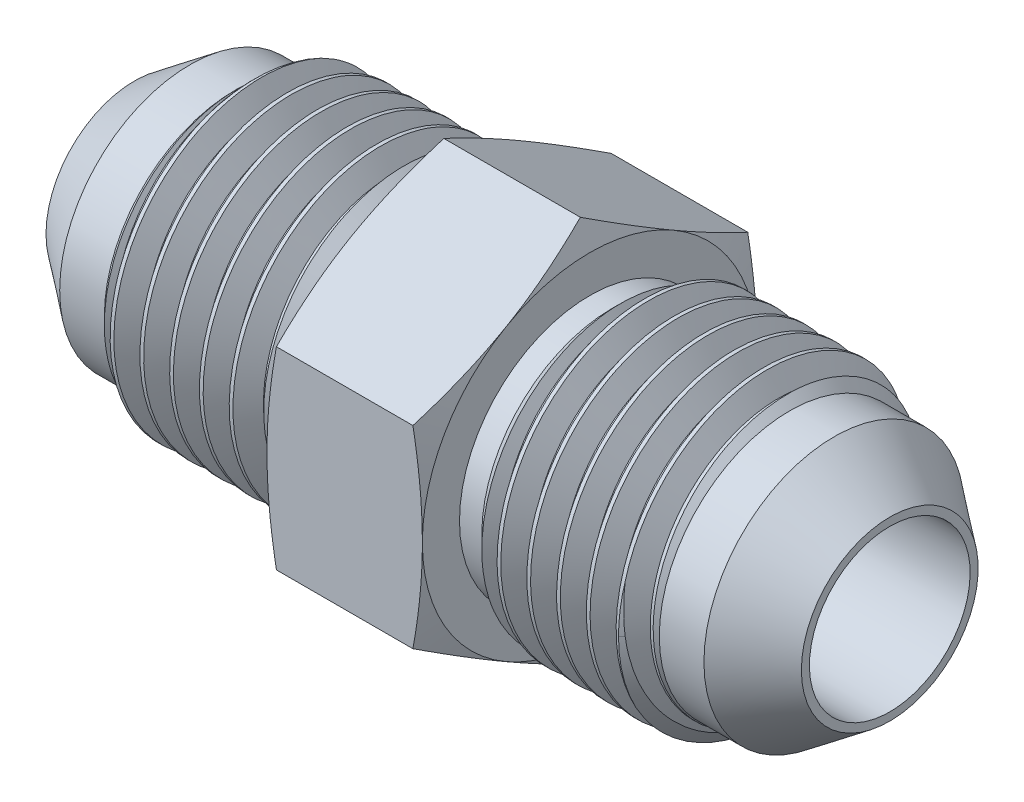
SolidWorks part; units mm, degrees
ref_plane "Front" through (0, 0, 0) normal (0, 0, 1) x (1, 0, 0)
ref_plane "Top" through (0, 0, 0) normal (0, 1, 0) x (1, 0, 0)
ref_plane "Right" through (0, 0, 0) normal (1, 0, 0) x (0, 0, -1)
sketch "Sketch6" plane through (0, 0, 0) normal (0, 0, 1) x (1, 0, 0)
  line L1 (17.907, 7.1437) -> (17.907, -7.1437) construction
  line L2 (-17.907, 0) -> (17.907, 0)
  line L4 (-17.907, 0) -> (-17.907, 7.1438)
  line L5 (-17.907, 7.1438) -> (17.907, 7.1437)
  line L6 (17.907, 0) -> (17.907, 7.1437)
  point P4 (3.683, 0)
  point P6 (-3.683, 0)
  dimension "Straight Dia" = 14.2875
  dimension "Length" = 35.814
  dimension "L1" = 14.224
  dimension "D1" = 14.224
revolve "Revolve3" add sketch "Sketch6" angle 360 about L2
sketch "Sketch14" plane through (-17.907, 0, 0) normal (-1, 0, 0) x (0, 0, 1)
  circle A0 centre (0, 0) radius 7.1438
  circle A2 centre (0, 0) radius 7.1438 construction
curve "Helix/Spiral1" pitch 1.4111 height 37.2251 radius 7.1438 centre (-17.907, 0, 0) axis (1, 0, 0) start towards (0, 1, 0) parameters "Pitch"=1.4111
sketch "Sketch15" plane through (0, 0, 0) normal (0, 0, 1) x (1, 0, 0)
  line L0 (-19.1417, 7.1438) -> (-17.907, 7.1438)
  line L1 (-17.907, 7.1438) -> (-18.4362, 6.2272)
  line L2 (-18.4362, 6.2272) -> (-18.6126, 6.2272)
  line L3 (-18.6126, 6.2272) -> (-19.1417, 7.1438)
  line L4 (-18.5244, 6.2272) -> (-18.5244, 7.1438) construction
  line L5 (-18.8771, 6.6855) -> (-18.1716, 6.6855) construction
  dimension "D1" = 60
  dimension "D2" = 0.1764
  dimension "D3" = 0.7056
sweep "Cut-Sweep1" cut profiles "Sketch15" path "Helix/Spiral1" align with end faces yes
ref_plane "Plane1" through (-3.683, 0, 0) normal (1, 0, 0) x (0, 0, -1)
sketch "Sketch12" plane through (-3.683, 0, 0) normal (1, 0, 0) x (0, 0, -1)
  line L1 (0, 9.1654) -> (-7.9375, 4.5827)
  line L2 (-7.9375, 4.5827) -> (-7.9375, -4.5827)
  line L3 (-7.9375, -4.5827) -> (0, -9.1654)
  line L4 (0, -9.1654) -> (7.9375, -4.5827)
  line L5 (7.9375, -4.5827) -> (7.9375, 4.5827)
  line L6 (7.9375, 4.5827) -> (0, 9.1654)
  circle A0 centre (0, 0) radius 7.9375 construction
  dimension "Hex" = 15.875
extrude "Extrude1" add sketch "Sketch12" along normal up to vertex (7.366 mm away) up to point (3.683, 0, 0)
sketch "Sketch7" plane through (0, 0, 0) normal (0, 0, 1) x (1, 0, 0)
  line L0 (-17.907, 0) -> (-17.907, 3.81)
  line L2 (-17.907, 3.81) -> (17.907, 3.81)
  line L4 (17.907, 0) -> (17.907, 7.1437) construction
  line L11 (17.907, 3.81) -> (17.907, 0)
  line L12 (17.907, 0) -> (-17.907, 0)
  line L13 (-17.907, 3.81) -> (-17.907, -3.81) construction
  dimension "ID" = 7.62
revolve "Cut-Revolve5" cut sketch "Sketch7" angle 360 about L12
sketch "Sketch10" plane through (0, 0, 0) normal (0, 0, 1) x (1, 0, 0)
  line L0 (-17.907, 7.1438) -> (-17.907, 4.191)
  line L2 (-17.907, 4.191) -> (-15.2723, 6.1764)
  line L3 (-15.2723, 6.1764) -> (-13.1556, 6.1764)
  line L4 (-13.1556, 6.1764) -> (-12.1883, 7.1438)
  line L5 (-12.1883, 7.1438) -> (-17.907, 7.1438)
  line L6 (-5.7087, 7.1438) -> (-3.683, 7.1438)
  line L8 (-3.683, 7.1438) -> (-3.683, 6.1764)
  line L9 (-3.683, 6.1764) -> (-4.7413, 6.1764)
  line L11 (-4.7413, 6.1764) -> (-5.7087, 7.1438)
  line L13 (-17.907, 4.191) -> (-17.907, -4.191) construction
  line L14 (-17.907, 0) -> (0, 0) construction
  line L15 (-17.907, 0) -> (17.907, 0) construction
  line L16 (-3.683, 9.1654) -> (-3.683, 4.5827) construction
  line L17 (-17.907, 7.1438) -> (17.907, 7.1438) construction
  line L18 (0, 0) -> (0, 9.1654) construction
  line L19 (3.683, 9.1654) -> (-3.683, 9.1654) construction
  line L20 (4.7413, 6.1764) -> (5.7087, 7.1438)
  line L21 (3.683, 6.1764) -> (4.7413, 6.1764)
  line L22 (3.683, 7.1438) -> (3.683, 6.1764)
  line L23 (5.7087, 7.1438) -> (3.683, 7.1438)
  line L24 (12.1883, 7.1438) -> (17.907, 7.1438)
  line L25 (13.1556, 6.1764) -> (12.1883, 7.1438)
  line L26 (15.2723, 6.1764) -> (13.1556, 6.1764)
  line L27 (17.907, 4.191) -> (15.2723, 6.1764)
  line L28 (17.907, 7.1438) -> (17.907, 4.191)
  line L29 (-10.1459, -7.1437) -> (-10.1459, 7.1438) construction
  line L30 (0, 0) -> (-10.1459, 0) construction
  point P38 (-10.1459, -7.1437)
  dimension "D1" = 45
  dimension "D2" = 1.0583
  dimension "D3" = 45
  dimension "D4" = 37
  dimension "D5" = 8.382
  dimension "D6" = 2.1167
  dimension "D7" = 0.0508
  dimension "D8" = 7.7611
revolve "Cut-Revolve6" cut sketch "Sketch10" angle 360 about L2
sketch "Sketch16" plane through (-3.683, 0, 0) normal (-1, 0, 0) x (0, 0, 1)
  circle A0 centre (0, 0) radius 7.9375 construction
  circle A1 centre (0, 0) radius 7.9375
extrude "Cut-Extrude1" cut sketch "Sketch16" against normal through all draft 70 flip side to cut
sketch "Sketch17" plane through (3.683, 0, 0) normal (1, 0, 0) x (0, 0, -1)
  circle A1 centre (0, 0) radius 7.9375
  circle A2 centre (0, 0) radius 7.9375
  dimension "D1" = 0
extrude "Cut-Extrude2" cut sketch "Sketch17" against normal through all draft 70 flip side to cut
equation "\"D1@Sketch6\" = \"L1@Sketch6\""
equation "\"D2@Sketch15\" = \"Pitch@Helix/Spiral1\"*.125"
equation "\"D3@Sketch15\" = \"Pitch@Helix/Spiral1\"*.50"
equation "\"D3@Helix/Spiral1\" = \"Length@Sketch6\"+\"Pitch@Helix/Spiral1\""
equation "\"D2@Sketch10\" = \"Pitch@Helix/Spiral1\"*.750"
equation "\"D5@Sketch10\" = \"ID@Sketch7\"*1.1"
equation "\"D6@Sketch10\" = \"Pitch@Helix/Spiral1\"*1.50"
equation "\"D8@Sketch10\" = \"Pitch@Helix/Spiral1\"*5.50"
